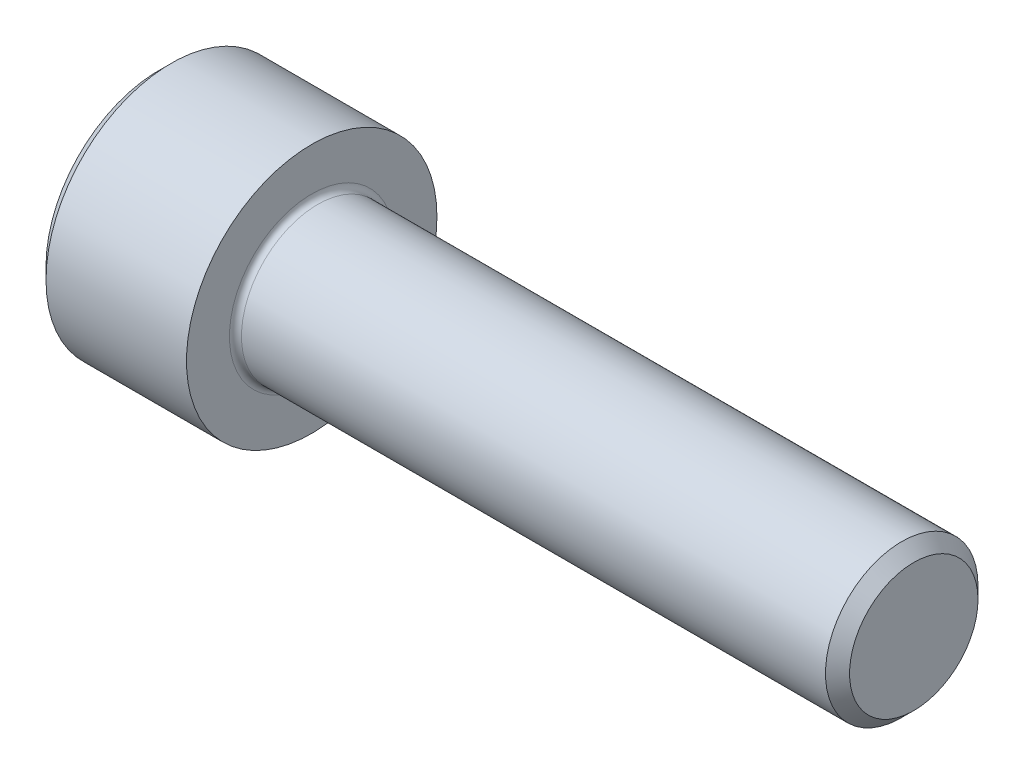
SolidWorks part; units mm, degrees
material "Alloy Steel"
ref_plane "Z Plane" through (0, 0, 0) normal (0, 0, 1) x (1, 0, 0)
ref_plane "Y Plane" through (0, 0, 0) normal (0, 1, 0) x (1, 0, 0)
ref_plane "X Plane" through (0, 0, 0) normal (1, 0, 0) x (0, 0, -1)
sketch "Sketch1" plane through (0, 0, 0) normal (0, 1, 0) x (1, 0, 0)
  line L0 (0, 3.9624) -> (0, -3.9624) construction
  line L1 (0, 0) -> (0, 3.9624)
  line L2 (0, 3.9624) -> (4.826, 3.9624)
  line L3 (4.826, 3.9624) -> (4.826, 2.413)
  line L4 (4.826, 2.413) -> (23.876, 2.413)
  line L5 (23.876, 2.413) -> (23.876, -2.413) construction
  line L6 (23.876, 2.413) -> (23.876, 0)
  line L7 (23.876, 0) -> (0, 0)
  line L8 (0, -3.9624) -> (1.6087, -3.9624) construction
  line L9 (1.6087, -3.9624) -> (3.2173, -3.9624) construction
  line L10 (3.2173, -3.9624) -> (4.826, -3.9624) construction
  point P2 (0, 0)
  point P5 (23.876, 0)
  dimension "Head Diameter" = 7.9248
  dimension "Thread Diameter" = 4.826
  dimension "Thread Length" = 19.05
revolve "Body" add sketch "Sketch1" angle 360 about L7
ref_plane "Plane1" through (3.2173, 0, 0) normal (1, 0, 0) x (0, 0, -1)
sketch "Sketch2" plane through (0, 0, 0) normal (-1, 0, 0) x (0, 0, 1)
  line L1 (-2.2914, 0) -> (-1.1457, -1.9844)
  line L2 (-1.1457, -1.9844) -> (1.1457, -1.9844)
  line L3 (1.1457, -1.9844) -> (2.2914, 0)
  line L4 (2.2914, 0) -> (1.1457, 1.9844)
  line L5 (1.1457, 1.9844) -> (-1.1457, 1.9844)
  line L6 (-1.1457, 1.9844) -> (-2.2914, 0)
  circle A0 centre (0, 0) radius 1.9844 construction
  dimension "Hex Head" = 3.9688
extrude "Hex" cut sketch "Sketch2" against normal up to surface (3.2173 mm away) up to plane "Plane1"
chamfer "Chamfer1" distance 0.381 angle 45 2 edges at (23.876, 0, -2.413) (0, 0, -3.9624)
fillet "Fillet1" radius 0.1905 1 edges at (4.826, 0, -2.413)
sketch "Sketch3" plane through (0, 0, 0) normal (1, 0, 0) x (0, 0, -1)
  circle A0 centre (0, 0) radius 2.2914
extrude "Hex Chamfer" cut sketch "Sketch3" along normal blind 2.54 draft 45
